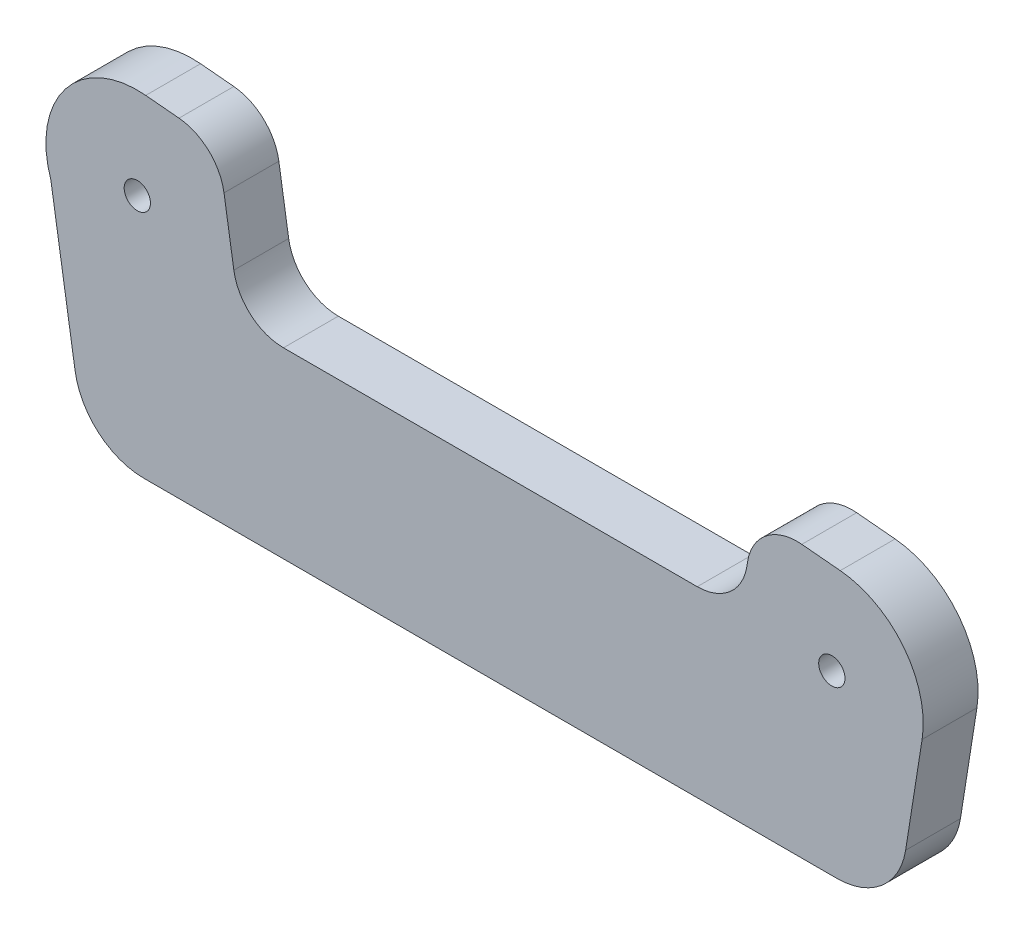
SolidWorks part; units mm, degrees
ref_plane "Front Plane" through (0, 0, 0) normal (0, 0, 1) x (1, 0, 0)
ref_plane "Top Plane" through (0, 0, 0) normal (0, 1, 0) x (1, 0, 0)
ref_plane "Right Plane" through (0, 0, 0) normal (1, 0, 0) x (0, 0, -1)
sketch "Sketch1" plane through (0, 0, 0) normal (0, 0, 1) x (1, 0, 0)
  line L0 (0, 0) -> (69.85, 0) construction
  line L1 (34.925, 0) -> (34.925, 19.3904) construction
  line L2 (-3.067, 19.3904) -> (72.917, 19.3904) construction
  line L3 (0, 0) -> (-3.067, 19.3904) construction
  line L4 (72.917, 19.3904) -> (69.85, 0) construction
  line L5 (-3.067, 19.3904) -> (-3.067, 26.4247) construction
  line L6 (72.917, 19.3904) -> (-3.067, 26.4247) construction
  line L7 (-8.8588, 0) -> (79.9743, 0)
  line L8 (-12.5245, 23.1759) -> (-8.8588, 0)
  line L11 (82.7942, 17.8281) -> (79.9743, 0)
  line L13 (-2.1452, 36.3821) -> (73.8388, 29.3478)
  circle A1 centre (-3.067, 26.4247) radius 1.4375
  circle A2 centre (72.917, 19.3904) radius 1.4375
  arc A6 (82.7942, 17.8281) -> (73.8388, 29.3478) centre (72.917, 19.3904) ccw
  arc A7 (3.7074, 19.0689) -> (4.0399, 19.3896) centre (-3.067, 26.4247) ccw
  circle A8 centre (-3.067, 26.4247) radius 10
  point P7 (34.925, 19.3904)
  dimension "D5" = 20
  dimension "D6" = 10
  dimension "D7" = 2.875
  dimension "D1" = 69.85
  dimension "D2" = 19.3904
  dimension "D3" = 75.984
  dimension "D4" = 7.0343
  dimension "D9" = 0
  dimension "D10" = 8.75
  dimension "D13" = 10
  dimension "D15" = 10
  dimension "bushing" = 2.875
extrude "Boss-Extrude1" add sketch "Sketch1" along normal blind 6 contours A8 L8 L7 L11 A6 L13 A7 A2 | A8 A7 A1 region at (37.3502, 15.4521, 0) region at (-10.7069, 32.4292, 0)
fillet "Fillet3" radius 7.62 2 edges at (79.9743, 0, 3) (-8.8588, 0, 3)
sketch "Sketch2" plane through (0, 0, 6) normal (0, 0, 1) x (1, 0, 0)
  line L0 (-2.1452, 36.3821) -> (73.8388, 29.3478) construction
  ellipse E0 centre (35.8468, 32.865) end of major axis (73.8388, 29.3478) minor radius 6.35
  dimension "D1" = 12.7
extrude "Cut-Extrude1" [suppressed] cut sketch "Sketch2" against normal through all
fillet "Fillet4" [suppressed] radius 6.35
sketch "Sketch3" plane through (0, 0, 6) normal (0, 0, 1) x (1, 0, 0)
  line L6 (5.7508, 35.6511) -> (8.2264, 20)
  line L7 (8.2264, 20) -> (62.8891, 20)
  line L8 (62.8891, 20) -> (64.5044, 30.2119)
  line L9 (64.5044, 30.2119) -> (5.7508, 35.6511)
  line L10 (-12.5245, 23.1759) -> (-9.8758, 6.4295) construction
  line L11 (82.7942, 17.8281) -> (80.9913, 6.4295) construction
  line L12 (-2.1452, 36.3821) -> (73.8388, 29.3478) construction
  line L13 (-2.3493, 0) -> (73.4649, 0) construction
  dimension "D1" = 20
  dimension "D2" = 20
  dimension "D3" = 20
extrude "Cut-Extrude2" cut sketch "Sketch3" against normal through all
fillet "Fillet5" radius 5.5 4 edges at (62.8891, 20, 3) (64.5044, 30.2119, 3) (8.2264, 20, 3) (5.7508, 35.6511, 3)
